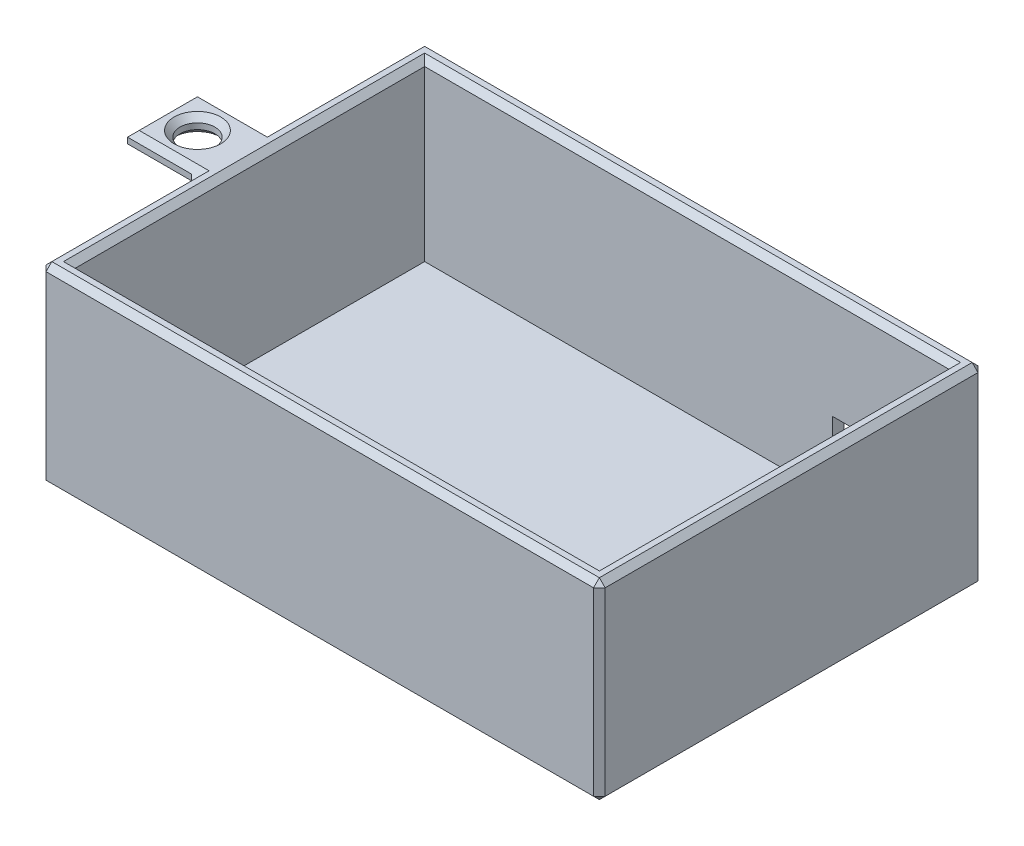
SolidWorks part; units mm, degrees
note: The reader was unsure of these and kept them because the rebuilt part matched: shared geometry of "草图2<3>".
ref_plane "前视基准面" through (0, 0, 0) normal (0, 0, 1) x (1, 0, 0)
ref_plane "上视基准面" through (0, 0, 0) normal (0, 1, 0) x (1, 0, 0)
ref_plane "右视基准面" through (0, 0, 0) normal (1, 0, 0) x (0, 0, -1)
other "Configuration Table"
sketch "草图1" plane through (0, 0, 0) normal (0, 1, 0) x (1, 0, 0)
  line L1 (0, 0) -> (80, 0)
  line L2 (0, 0) -> (0, -50)
  line L3 (0, -50) -> (80, -50)
  line L4 (80, 0) -> (80, -50)
  dimension "D1" = 80
  dimension "D2" = 50
extrude "凸台-拉伸1" add sketch "草图1" along normal blind 3
sketch "草图2" plane through (0, 0, 0) normal (0, -1, 0) x (1, 0, 0)
  line L0 (-8, 58) -> (-8, -8)
  line L1 (-8, -8) -> (88, -8)
  line L2 (88, -8) -> (88, 58)
  line L3 (88, 58) -> (-8, 58)
  line L8 (-5, 55) -> (-5, -5)
  line L9 (-5, -5) -> (85, -5)
  line L10 (85, -5) -> (85, 55)
  line L11 (85, 55) -> (-5, 55)
  line L12 (-5, 55) -> (-5, -5)
  line L13 (-5, -5) -> (85, -5)
  line L14 (85, -5) -> (85, 55)
  line L15 (85, 55) -> (-5, 55)
  line L20 (0, 50) -> (0, 0)
  line L21 (0, 0) -> (80, 0)
  line L22 (80, 0) -> (80, 50)
  line L23 (80, 50) -> (0, 50)
  line L24 (0, 50) -> (0, 0)
  line L25 (0, 0) -> (80, 0)
  line L26 (80, 0) -> (80, 50)
  line L27 (80, 50) -> (0, 50)
  line M9 (0, 50) -> (0, 0)
  line M10 (0, 0) -> (80, 0)
  line M11 (80, 0) -> (80, 50)
  line M12 (80, 50) -> (0, 50)
  dimension "D1" = 5
  dimension "D2" = 0
  dimension "D3" = 3
extrude "凸台-拉伸3" add sketch "草图2" against normal up to surface (3 mm away) contours L14 L15 L12 L13 M9 M12 M11 M10 up to face at (40, 3, 25)
extrude "凸台-拉伸4" add sketch "草图2<3>" against normal offset from surface (33 mm away) 33 contours L2 L3 L0 L1 L15 L14 L13 L12 up to face at (40, 0, 25)
sketch "草图2<3>" plane through (0, 0, 0) normal (0, -1, 0) x (1, 0, 0) same geometry as "草图2"
sketch "草图3" plane through (0, 0, -8) normal (0, 0, -1) x (-1, 0, 0)
  line L0 (-85, 33) -> (-85, 3) construction
  line L1 (-85, 3) -> (-65, 3)
  line L2 (-85, 3) -> (-85, 15)
  line L3 (-85, 15) -> (-65, 15)
  line L4 (-65, 3) -> (-65, 15)
  line L5 (5, 3) -> (-85, 3) construction
  dimension "D1" = 12
  dimension "D2" = 20
extrude "切除-拉伸1" cut sketch "草图3" against normal blind 10
sketch "草图4" plane through (0, 33, 0) normal (0, 1, 0) x (1, 0, 0)
  line L0 (-8, -58) -> (-8, 8) construction
  line L2 (-8, -25) -> (-8, -19)
  line L3 (-8, -19) -> (-20, -19)
  line L4 (-20, -25) -> (-20, -19)
  line L5 (-8, -25) -> (-20, -25) construction
  line L7 (-20, -25) -> (-20, -31)
  line L8 (-20, -31) -> (-8, -31)
  line L9 (-8, -25) -> (-8, -31)
  circle A0 centre (-14, -25) radius 3
  point P8 (-14, -25)
  point P11 (0, 0)
  point P12 (0, 0)
  point P13 (0, 0)
  dimension "D3" = 6
  dimension "D1" = 12
  dimension "D2" = 12
  dimension "D4" = 6
extrude "凸台-拉伸5" add sketch "草图4" against normal blind 3
chamfer "倒角1" distance 1 angle 45 25 edges at (75, 3, -8) (65, 9, -8) (75, 15, -8) (85, 9, -8) (-14, 33, 28) (40, 33, -5) (-5, 33, 25) (40, 33, 55) (85, 33, 25) (88, 16.5, -8) (-8, 16.5, -8) (-8, 16.5, 58) (40, 33, -8) (40, 0, -8) (-8, 0, 25) (40, 33, 58) (40, 0, 58) (88, 33, 25) (88, 0, 25) (88, 16.5, 58) (-8, 33, 44.5) (-14, 33, 31) (-20, 33, 25) (-14, 33, 19) (-8, 33, 5.5)
chamfer "倒角2" distance 1 angle 45 7 edges at (-8, 31, 19) (-8, 31, 31) (-14, 30, 19) (-20, 30, 25) (-14, 30, 31) (-8, 30, 25) (-14, 30, 28)
